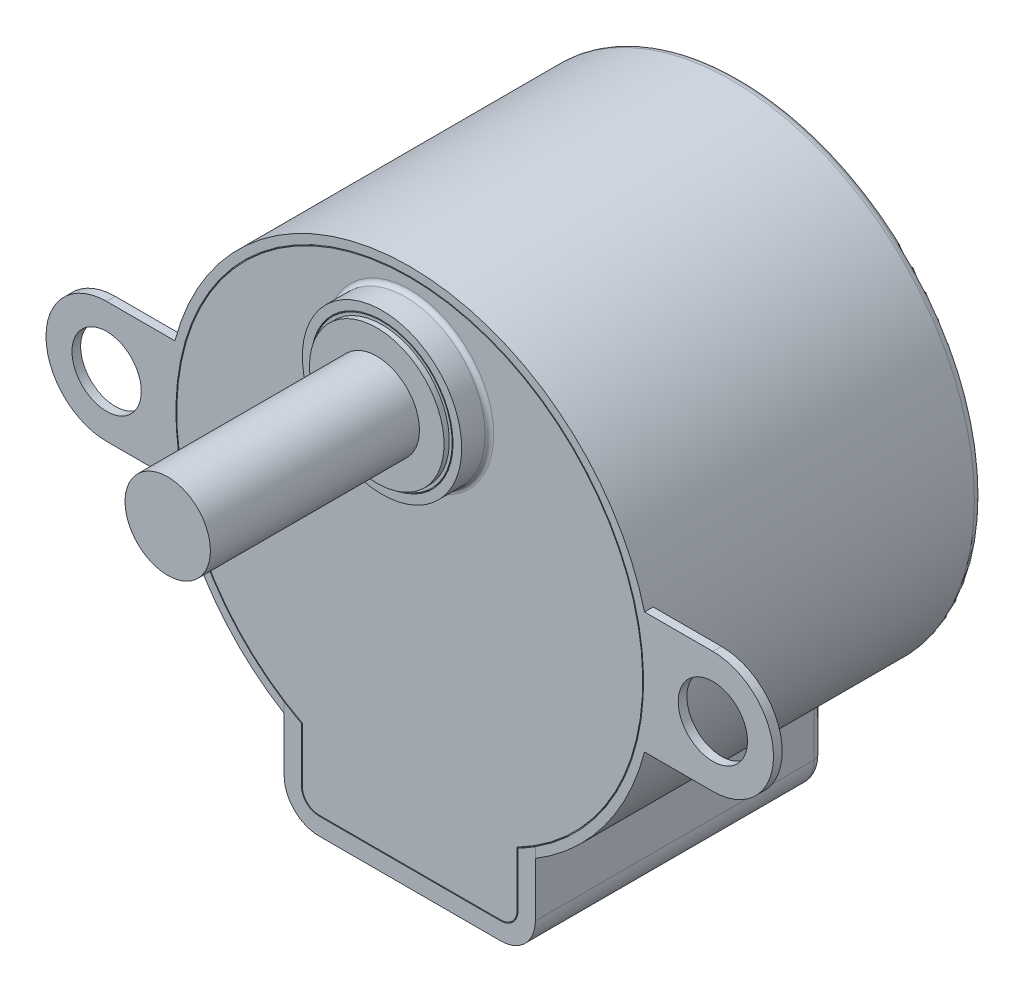
SolidWorks part; units mm, degrees
material "Chrome Stainless Steel"
ref_plane "Alzado" through (0, 0, 0) normal (0, 0, 1) x (1, 0, 0)
ref_plane "Planta" through (0, 0, 0) normal (0, 1, 0) x (1, 0, 0)
ref_plane "Vista lateral" through (0, 0, 0) normal (1, 0, 0) x (0, 0, -1)
sketch "Croquis1" plane through (0, 0, 0) normal (0, 0, 1) x (1, 0, 0)
  circle A0 centre (0, 0) radius 14
  dimension "D1" = 28
extrude "Saliente-Extruir1" add sketch "Croquis1" against normal blind 19.1
sketch "Croquis2" plane through (0, 0, 0) normal (0, 0, 1) x (1, 0, 0)
  line L0 (-13.5554, 3.5) -> (-17.5, 3.5)
  line L1 (-17.5, -3.5) -> (-13.5554, -3.5)
  line L2 (0, 0) -> (0, 3.9446) construction
  circle A0 centre (-17.5, 0) radius 2
  arc A1 (-17.5, 3.5) -> (-17.5, -3.5) centre (-17.5, 0) ccw
  arc A2 (-13.5554, 3.5) -> (-13.5554, -3.5) centre (0, 0) ccw
  circle A3 centre (0, 0) radius 14 construction
  dimension "D1" = 35
  dimension "D2" = 3.5
  dimension "D3" = 4
extrude "Saliente-Extruir2" add sketch "Croquis2" against normal blind 0.5
mirror "Simetría1" about plane through (0, 0, 0) normal (1, 0, 0) of "Saliente-Extruir2"
sketch "Croquis3" plane through (0, 0, 0) normal (0, 0, 1) x (1, 0, 0)
  circle A0 centre (0, 0) radius 13.5
  arc A1 (13.5554, 3.5) -> (-13.5554, 3.5) centre (0, 0) ccw construction
  dimension "D1" = 0.5
split line "Línea de partición1"
sketch "Croquis4" plane through (0, 0, 0) normal (0, 0, 1) x (1, 0, 0)
  line L0 (0, -11.388) -> (0, 0) construction
  line L1 (-7.25, -11.388) -> (7.25, -11.388) construction
  line L2 (-7.25, -11.388) -> (-7.25, -18.3526)
  line L3 (-7.25, -18.3526) -> (7.25, -18.3526)
  line L4 (7.25, -11.388) -> (7.25, -18.3526)
  circle A0 centre (0, 0) radius 13.5 construction
  arc A1 (-7.25, -11.388) -> (7.25, -11.388) centre (0, 0) ccw
  dimension "D1" = 14.5
extrude "Cortar-Extruir1" cut sketch "Croquis4" against normal blind 16.6
sketch "Croquis5" plane through (0, 0, 0) normal (0, 0, 1) x (1, 0, 0)
  line L0 (-7.25, -11.388) -> (-7.25, -17.1)
  line L1 (-7.25, -17.1) -> (7.25, -17.1)
  line L2 (7.25, -17.1) -> (7.25, -11.388)
  arc A0 (-7.25, -11.388) -> (7.25, -11.388) centre (0, 0) ccw
  arc A1 (7.25, -11.388) -> (-7.25, -11.388) centre (0, 0) ccw construction
  arc A2 (17.5, -3.5) -> (17.5, 3.5) centre (17.5, 0) ccw construction
  dimension "D1" = 17.1
extrude "Saliente-Extruir3" add sketch "Croquis5" against normal up to surface (16.6 mm away) separate body up to face at (0, -12.7161, -16.6)
fillet "Redondeo1" radius 2 2 edges at (7.25, -17.1, -8.3) (-7.25, -17.1, -8.3)
sketch "Croquis6" plane through (0, 0, 0) normal (0, 0, 1) x (1, 0, 0)
  line L0 (-6.25, -11.388) -> (-6.25, -15.1)
  line L1 (-5.25, -16.1) -> (5.25, -16.1)
  line L2 (6.25, -15.1) -> (6.25, -11.388)
  line L3 (-5.25, -17.1) -> (5.25, -17.1)
  line L4 (7.25, -15.1) -> (7.25, -11.388)
  line L5 (-7.25, -11.388) -> (-7.25, -15.1)
  line L6 (-5.25, -17.1) -> (5.25, -17.1)
  line L7 (7.25, -15.1) -> (7.25, -11.388)
  line L8 (-7.25, -11.388) -> (-7.25, -15.1)
  line L9 (-6.25, -11.388) -> (6.25, -11.388)
  arc A0 (-6.25, -15.1) -> (-5.25, -16.1) centre (-5.25, -15.1) ccw
  arc A1 (5.25, -16.1) -> (6.25, -15.1) centre (5.25, -15.1) ccw
  arc A3 (5.25, -17.1) -> (7.25, -15.1) centre (5.25, -15.1) ccw
  arc A4 (-7.25, -11.388) -> (7.25, -11.388) centre (0, 0) ccw
  arc A5 (-7.25, -15.1) -> (-5.25, -17.1) centre (-5.25, -15.1) ccw
  arc A6 (5.25, -17.1) -> (7.25, -15.1) centre (5.25, -15.1) ccw
  arc A7 (-7.25, -11.388) -> (7.25, -11.388) centre (0, 0) ccw construction
  arc A8 (-7.25, -15.1) -> (-5.25, -17.1) centre (-5.25, -15.1) ccw
  arc M10 (7.25, -11.388) -> (-7.25, -11.388) centre (0, 0) cw
  dimension "D1" = 0
  dimension "D2" = 1
extrude "Cortar-Extruir2" cut sketch "Croquis6" against normal blind 1 contours L1 A1 L2 L0 A0 M10 region at (0, -14.5021, 0)
extrude "Saliente-Extruir4" add sketch "Croquis6<3>" against normal blind 0.5 contours L1 A1 L2 L0 A0 M10 region at (0, -14.5021, 0)
sketch "Croquis6<3>" plane through (0, 0, 0) normal (0, 0, 1) x (1, 0, 0) same geometry as "Croquis6"
fillet "Redondeo2" radius 0.5 1 edges at (14, 0, -19.1)
sketch "Croquis7" plane through (0, 0, 0) normal (0, 0, 1) x (1, 0, 0)
  circle A0 centre (0, 8) radius 4.6
  dimension "D1" = 9.2
  dimension "D2" = 8
extrude "Saliente-Extruir5" add sketch "Croquis7" along normal blind 1.6
sketch "Croquis8" plane through (0, 0, 1.6) normal (0, 0, 1) x (1, 0, 0)
  circle A0 centre (0, 8) radius 2.5
  dimension "D1" = 5
extrude "Saliente-Extruir6" [suppressed] add sketch "Croquis8" along normal blind 8.4 separate body
sketch "Croquis9" [suppressed] plane through (0, 0, 10) normal (0, 0, 1) x (1, 0, 0)
  line L1 (-1.5, 10) -> (-2.5, 10)
  line L2 (-1.5, 10) -> (-1.5, 6)
  line L3 (-1.5, 6) -> (-2.5, 6)
  line L4 (-2.5, 10) -> (-2.5, 6)
  line L5 (1.5, 10) -> (2.5, 10)
  line L6 (1.5, 10) -> (1.5, 6)
  line L7 (1.5, 6) -> (2.5, 6)
  line L8 (2.5, 10) -> (2.5, 6)
  circle A0 centre (0, 8) radius 2.5 construction
  dimension "D1" = 3
extrude "Cortar-Extruir3" [suppressed] cut sketch "Croquis9" against normal blind 6
fillet "Redondeo3" radius 0.5 5 edges at (7.25, -13.244, -16.6) (6.6642, -16.5142, -16.6) (0, -17.1, -16.6) (-6.6642, -16.5142, -16.6) (-7.25, -13.244, -16.6)
fillet "Redondeo4" radius 0.25 1 edges at (4.6, 8, 0)
sketch "Croquis10" plane through (0, 0, 1.6) normal (0, 0, 1) x (1, 0, 0)
  circle A0 centre (0, 8) radius 4.1
  circle A1 centre (0, 8) radius 4.6 construction
  dimension "D1" = 0.5
split line "Línea de partición2"
sketch "Croquis11" plane through (0, 0, 0) normal (0, 0, 1) x (1, 0, 0)
  line L9 (-6.2, -11.9358) -> (-6.2, -15.1)
  line L10 (-5.25, -16.05) -> (5.25, -16.05)
  line L11 (6.2, -15.1) -> (6.2, -11.9358)
  line L12 (-6.2, -11.9358) -> (-6.2, -15.1)
  line L13 (-5.25, -16.05) -> (5.25, -16.05)
  line L14 (6.2, -15.1) -> (6.2, -11.9358)
  arc A15 (6.2, -11.9358) -> (7.2231, -11.3459) centre (0, 0) ccw
  arc A16 (7.2231, -11.3459) -> (-7.2231, -11.3459) centre (0, 0) ccw
  arc A17 (-7.2231, -11.3459) -> (-6.2, -11.9358) centre (0, 0) ccw
  arc A18 (-6.2, -15.1) -> (-5.25, -16.05) centre (-5.25, -15.1) ccw
  arc A19 (5.25, -16.05) -> (6.2, -15.1) centre (5.25, -15.1) ccw
  arc A20 (6.2, -11.9358) -> (7.2231, -11.3459) centre (0, 0) ccw
  arc A21 (7.2231, -11.3459) -> (-7.2231, -11.3459) centre (0, 0) ccw
  arc A22 (-7.2231, -11.3459) -> (-6.2, -11.9358) centre (0, 0) ccw
  arc A23 (-6.2, -15.1) -> (-5.25, -16.05) centre (-5.25, -15.1) ccw
  arc A24 (5.25, -16.05) -> (6.2, -15.1) centre (5.25, -15.1) ccw
  arc M10 (6.25, -11.9661) -> (7.25, -11.388) centre (0, 0) ccw
  arc M11 (7.25, -11.388) -> (-7.25, -11.388) centre (0, 0) ccw
  arc M12 (-7.25, -11.388) -> (-6.25, -11.9661) centre (0, 0) ccw
  line M13 (-6.25, -11.9661) -> (-6.25, -15.1)
  arc M14 (-6.25, -15.1) -> (-5.25, -16.1) centre (-5.25, -15.1) ccw
  line M15 (-5.25, -16.1) -> (5.25, -16.1)
  arc M16 (5.25, -16.1) -> (6.25, -15.1) centre (5.25, -15.1) ccw
  line M17 (6.25, -15.1) -> (6.25, -11.9661)
  dimension "D1" = 0.05
extrude "Cortar-Extruir4" cut sketch "Croquis11" against normal blind 0.1 contours A24 L13 A23 L12 A22 A21 A20 L14 M17 M10 M11 M12 M13 M14 M15 M16 region at (6.2099, -13.533, 0)
sketch "Croquis12" plane through (0, 0, 1.6) normal (0, 0, 1) x (1, 0, 0)
  circle A3 centre (0, 8) radius 4.05
  circle A4 centre (0, 8) radius 4.05
  circle M2 centre (0, 8) radius 4.1
  dimension "D1" = 0.05
extrude "Cortar-Extruir5" cut sketch "Croquis12" against normal blind 0.1 contours A4 M2 region at (-4.0884, 8, 1.6)
sketch "Croquis14" plane through (0, 0, -19.1) normal (0, 0, -1) x (-1, 0, 0)
  line L0 (-12.5, 1.5) -> (12.5, 1.5) construction
  line L1 (0, 1.5) -> (0, 0) construction
  line L2 (-7.5, -5) -> (7.5, -5) construction
  line L3 (0, 0) -> (0, -5) construction
  text T0 "28BYJ-48" font "Century Gothic" height 3.5
  text T1 "5V - DC" font "Century Gothic" height 2
  dimension "D1" = 25
  dimension "D2" = 1.5
  dimension "D3" = 15
  dimension "D4" = 5
extrude "Saliente-Extruir7" add sketch "Croquis14" along normal blind 0.1 separate body
chamfer "Chaflán1" [suppressed] distance 0.5 angle 45
sketch "Sketch1" plane through (0, 0, 1.6) normal (0, 0, 1) x (1, 0, 0)
  circle A0 centre (0, 8) radius 2.4638
  circle A1 centre (0, 8) radius 3.8862
  dimension "D1" = 4.9276
  dimension "D2" = 7.7724
extrude "Boss-Extrude2" add sketch "Sketch1" along normal blind 12.3724 contours A0 region at (0, 8, 1.6)
extrude "Boss-Extrude3" add sketch "Sketch1<4>" along normal blind 0.3048
sketch "Sketch1<4>" plane through (0, 0, 1.6) normal (0, 0, 1) x (1, 0, 0) same geometry as "Sketch1"
